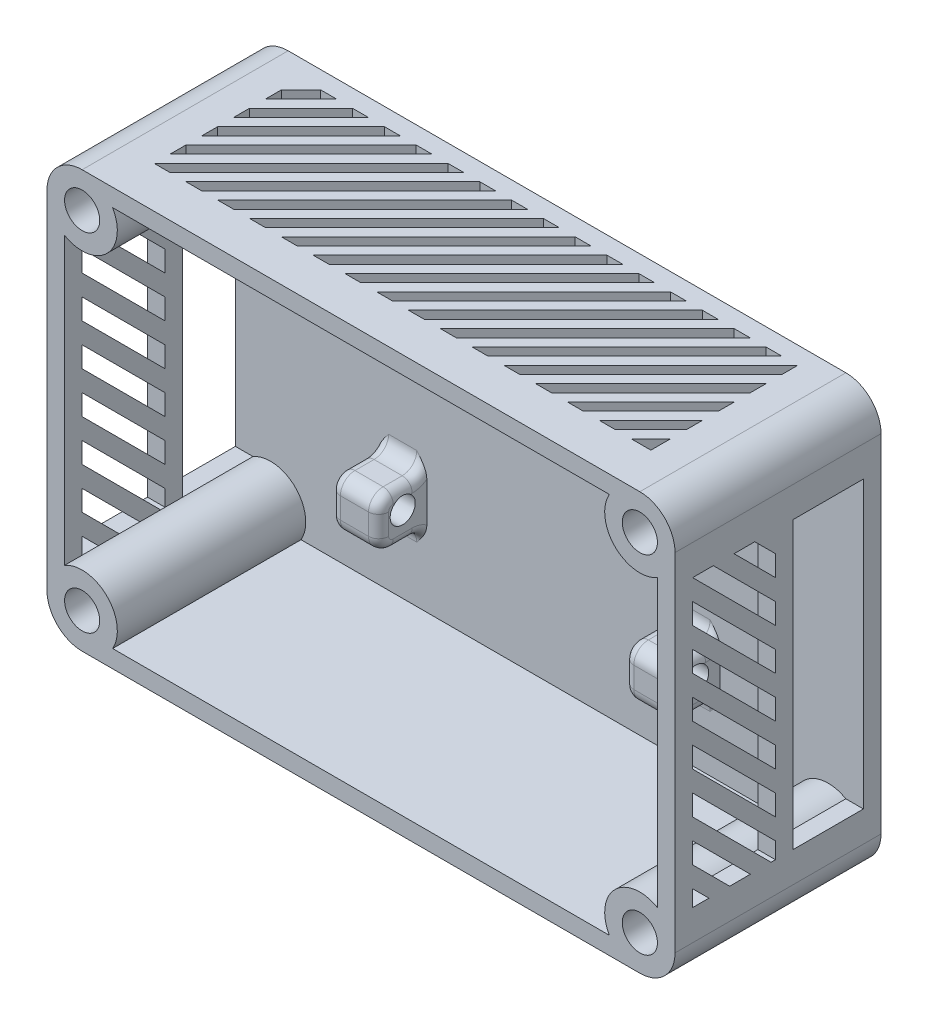
SolidWorks part; units mm, degrees
note: The reader was unsure of these and kept them because the rebuilt part matched: shared geometry of "Esquisse1<4>", "Esquisse1<5>".
ref_plane "Plan de face" through (0, 0, 0) normal (0, 0, 1) x (1, 0, 0)
ref_plane "Plan de dessus" through (0, 0, 0) normal (0, 1, 0) x (1, 0, 0)
ref_plane "Plan de droite" through (0, 0, 0) normal (1, 0, 0) x (0, 0, -1)
sketch "Esquisse1" plane through (0, 0, 0) normal (0, 0, 1) x (1, 0, 0)
  line L1 (-27.75, 17.25) -> (27.75, 17.25) construction
  line L2 (-27.75, 17.25) -> (-27.75, -17.25) construction
  line L3 (-27.75, -17.25) -> (27.75, -17.25) construction
  line L4 (27.75, 17.25) -> (27.75, -17.25) construction
  line L12 (-31.25, -20.75) -> (31.25, -20.75)
  line L13 (31.25, 20.75) -> (31.25, -20.75)
  line L14 (-31.25, 20.75) -> (31.25, 20.75)
  line L15 (-31.25, 20.75) -> (-31.25, -20.75)
  line L16 (-22.75, 12.25) -> (-22.75, -12.25)
  line L17 (-22.75, -12.25) -> (22.75, -12.25)
  line L18 (22.75, 12.25) -> (22.75, -12.25)
  line L19 (-22.75, 12.25) -> (22.75, 12.25)
  circle A0 centre (-27.75, 17.25) radius 1.75
  circle A1 centre (27.75, 17.25) radius 1.75
  circle A2 centre (27.75, -17.25) radius 1.75
  circle A3 centre (-27.75, -17.25) radius 1.75
  point P4 (-27.75, 0)
  point P6 (0, 17.25)
  dimension "D3" = 3.5
  dimension "D1" = 34.5
  dimension "D2" = 55.5
  dimension "D4" = 3.5
  dimension "D5" = 5
extrude "Boss.-Extru.1" add sketch "Esquisse1" along normal blind 17.5 contours A0 | L14 L15 L12 L13 A3 A2 A1 A0 | A3 | A2 | A1 | L19 L16 L17 L18
extrude "Boss.-Extru.2" add sketch "Esquisse1<4>" against normal blind 3 contours L19 L16 L17 L18 | L14 L15 L12 L13 A3 A2 A1 A0 L16 L19 L18 L17
sketch "Esquisse1<4>" plane through (0, 0, 0) normal (0, 0, 1) x (1, 0, 0) same geometry as "Esquisse1"
extrude "Enlèv. mat.-Extru.1" cut sketch "Esquisse1<5>" against normal up to next (3 mm away) and the other way up to next (17.5 mm away) contours A3 | A0 | A1 | A2
sketch "Esquisse1<5>" plane through (0, 0, 0) normal (0, 0, 1) x (1, 0, 0) same geometry as "Esquisse1"
shell "Coque1" thickness 1.75
fillet "Congé1" radius 3.5 4 edges at (-31.25, -20.75, 7.25) (-31.25, 20.75, 7.25) (31.25, -20.75, 7.25) (31.25, 20.75, 7.25)
sketch "Esquisse2" plane through (0, 0, -1.25) normal (0, 0, 1) x (1, 0, 0)
  line L1 (-17, -7) -> (-12.2, -7)
  line L2 (-17, -7) -> (-17, -12)
  line L3 (-17, -12) -> (-12.2, -12)
  line L4 (-12.2, -7) -> (-12.2, -12)
  line L5 (-17, 12) -> (-12.2, 12)
  line L6 (-17, 12) -> (-17, 7)
  line L7 (-17, 7) -> (-12.2, 7)
  line L8 (-12.2, 12) -> (-12.2, 7)
  line L9 (12.2, 12) -> (17, 12)
  line L10 (12.2, 12) -> (12.2, 7)
  line L11 (12.2, 7) -> (17, 7)
  line L12 (17, 12) -> (17, 7)
  line L13 (12.2, -12) -> (17, -12)
  line L14 (12.2, -12) -> (12.2, -7)
  line L15 (12.2, -7) -> (17, -7)
  line L16 (17, -12) -> (17, -7)
  line L17 (-12.2, 12) -> (12.2, 12) construction
  line L18 (-12.2, 12) -> (-12.2, -12) construction
  line L19 (-12.2, -12) -> (12.2, -12) construction
  line L20 (12.2, 12) -> (12.2, -12) construction
  point P16 (0, 12)
  point P18 (-12.2, 0)
  dimension "D1" = 24.4
  dimension "D2" = 14
  dimension "D3" = 24
  dimension "D4" = 4.8
extrude "Boss.-Extru.3" add sketch "Esquisse2" along normal blind 4.8
sketch "Esquisse3" plane through (12.2, 0, 0) normal (-1, 0, 0) x (0, 0, 1)
  line L0 (1.15, -9) -> (1.15, 9) construction
  line L1 (-3, 17.25) -> (-3, -17.25) construction
  circle A0 centre (1.15, -9) radius 1.25
  circle A1 centre (1.15, 9) radius 1.25
  point P2 (1.15, 0)
  dimension "D1" = 2.5
  dimension "D2" = 18
  dimension "D3" = 4.15
extrude "Enlèv. mat.-Extru.2" cut sketch "Esquisse3" against normal up to next and the other way up to next
sketch "Esquisse4" plane through (-31.25, 0, 0) normal (-1, 0, 0) x (0, 0, 1)
  line L0 (7.5, 14.2189) -> (8.5313, 13.1877) construction
  line L1 (-1.25, -14.2189) -> (5.75, -14.2189)
  line L2 (-1.25, -14.2189) -> (-1.25, 14.2189)
  line L3 (-1.25, 14.2189) -> (5.75, 14.2189)
  line L4 (5.75, -14.2189) -> (5.75, 14.2189)
  line L5 (-1.25, 14.2189) -> (-1.25, -14.2189) construction
  line L6 (-1.25, 0) -> (-3, 0) construction
  line L7 (7.5, 14.2189) -> (15.75, 14.2189)
  line L8 (7.5, 14.2189) -> (7.5, -14.2189)
  line L9 (7.5, -14.2189) -> (15.75, -14.2189)
  line L10 (15.75, 14.2189) -> (15.75, -14.2189)
  line L11 (-3, 17.25) -> (-3, -17.25) construction
  line L12 (5.75, 0) -> (7.5, 0) construction
  line L13 (15.75, 0) -> (17.5, 0) construction
  line L14 (17.5, 17.25) -> (17.5, -17.25) construction
  line L15 (9.5625, 14.2189) -> (7.5, 12.1564)
  line L16 (11.625, 14.2189) -> (7.5, 10.0939)
  line L17 (8.5313, 13.1877) -> (9.5625, 12.1564) construction
  line L18 (13.6875, 14.2189) -> (7.5, 8.0314)
  line L19 (9.5625, 12.1564) -> (10.5938, 11.1252) construction
  line L20 (15.75, 14.2189) -> (7.5, 5.9689)
  line L21 (10.5938, 11.1252) -> (11.625, 10.0939) construction
  line L22 (15.75, 12.1564) -> (7.5, 3.9064)
  line L23 (15.75, 10.0939) -> (7.5, 1.8439)
  line L24 (15.75, 8.0314) -> (7.5, -0.2186)
  line L25 (15.75, 5.9689) -> (7.5, -2.2811)
  line L26 (15.75, 3.9064) -> (7.5, -4.3436)
  line L27 (15.75, 1.8439) -> (7.5, -6.4061)
  line L28 (7.5, -8.4686) -> (15.75, -0.2186)
  line L29 (7.5, -10.5311) -> (15.75, -2.2811)
  line L30 (7.5, -12.5936) -> (15.75, -4.3436)
  line L31 (11.625, 10.0939) -> (12.6562, 9.0627) construction
  line L32 (12.6562, 9.0627) -> (13.6875, 8.0314) construction
  line L33 (13.6875, 8.0314) -> (14.7187, 7.0002) construction
  line L34 (8.5313, 2.8752) -> (9.5625, 1.8439) construction
  line L35 (9.5625, 1.8439) -> (10.5938, 0.8127) construction
  line L36 (10.5938, 0.8127) -> (11.625, -0.2186) construction
  line L37 (11.625, -0.2186) -> (12.6562, -1.2498) construction
  line L38 (12.6562, -1.2498) -> (13.6875, -2.2811) construction
  line L39 (7.9372, -14.2189) -> (15.75, -6.4061)
  line L40 (13.6875, -2.2811) -> (14.7187, -3.3123) construction
  line L41 (9.9997, -14.2189) -> (15.75, -8.4686)
  line L42 (12.0622, -14.2189) -> (15.75, -10.5311)
  line L43 (14.1247, -14.2189) -> (15.75, -12.5936)
  line L44 (14.9373, -13.4062) -> (13.9061, -12.375) construction
  line L48 (7.5, -8.4686) -> (8.5312, -9.4998) construction
  line L49 (8.5312, -9.4998) -> (9.5625, -10.5311) construction
  line L50 (9.5625, -10.5311) -> (10.5937, -11.5623) construction
  line L51 (10.5937, -11.5623) -> (11.625, -12.5936) construction
  line L52 (11.625, -12.5936) -> (12.6562, -13.6248) construction
  line L53 (12.6562, -13.6248) -> (13.2503, -14.2189) construction
  line L54 (14.9373, -13.4062) -> (15.75, -14.2189) construction
  point P4 (2.25, 14.2189)
  point P6 (-1.25, 0)
  dimension "D1" = 45
  dimension "D2" = 7
extrude "Enlèv. mat.-Extru.3" cut sketch "Esquisse4" against normal up to next contours L1 L4 L3 L2 | L16 L7 L15 L8 | L20 L7 L18 L8 | L23 L10 L22 L8 | L25 L10 L24 L8 | L27 L10 L26 L8 | L8 L29 L10 L28 | L9 L39 L10 L30 L8 | L9 L42 L10 L41 | L43 L9 L10
mirror "Symétrie1" about plane through (0, 0, 0) normal (1, 0, 0) of "Enlèv. mat.-Extru.3"
sketch "Esquisse5" plane through (0, 20.75, 0) normal (0, 1, 0) x (1, 0, 0)
  line L0 (-24.7189, 1.25) -> (24.7189, 1.25) construction
  line L1 (-24.7189, 1.25) -> (24.7189, 1.25)
  line L2 (-24.7189, 1.25) -> (-24.7189, -13.3718)
  line L3 (-24.7189, -13.3718) -> (24.7189, -13.3718)
  line L4 (24.7189, 1.25) -> (24.7189, -13.3718)
  line L6 (0, 1.25) -> (0, 3) construction
  line L8 (23.7382, -12.3911) -> (22.9469, -11.5998) construction
  line L10 (-24.7189, -3.8765) -> (-19.5924, 1.25)
  line L11 (-23.1364, -3.8765) -> (-18.0098, 1.25)
  line L12 (-21.5538, -3.8765) -> (-16.4273, 1.25)
  line L13 (-19.9713, -3.8765) -> (-14.8447, 1.25)
  line L14 (-18.3887, -3.8765) -> (-13.2622, 1.25)
  line L15 (-16.8062, -3.8765) -> (-11.6797, 1.25)
  line L16 (-15.2236, -3.8765) -> (-10.0971, 1.25)
  line L17 (-13.6411, -3.8765) -> (-8.5146, 1.25)
  line L18 (-12.0585, -3.8765) -> (-6.932, 1.25)
  line L19 (-10.476, -3.8765) -> (-5.3495, 1.25)
  line L20 (-8.8934, -3.8765) -> (-3.7669, 1.25)
  line L21 (-7.3109, -3.8765) -> (-2.1844, 1.25)
  line L22 (-5.7284, -3.8765) -> (-0.6018, 1.25)
  line L23 (-4.1458, -3.8765) -> (0.9807, 1.25)
  line L24 (-2.5633, -3.8765) -> (2.5633, 1.25)
  line L25 (-0.9807, -3.8765) -> (4.1458, 1.25)
  line L26 (0.6018, -3.8765) -> (5.7284, 1.25)
  line L27 (2.1844, -3.8765) -> (7.3109, 1.25)
  line L28 (3.7669, -3.8765) -> (8.8934, 1.25)
  line L29 (5.3495, -3.8765) -> (10.476, 1.25)
  line L30 (6.932, -3.8765) -> (12.0585, 1.25)
  line L31 (8.5146, -3.8765) -> (13.6411, 1.25)
  line L32 (10.0971, -3.8765) -> (15.2236, 1.25)
  line L33 (11.6797, -3.8765) -> (16.8062, 1.25)
  line L34 (13.2622, -3.8765) -> (18.3887, 1.25)
  line L35 (14.8447, -3.8765) -> (19.9713, 1.25)
  line L36 (16.4273, -3.8765) -> (21.5538, 1.25)
  line L37 (18.0098, -3.8765) -> (23.1364, 1.25)
  line L38 (19.5924, -3.8765) -> (24.7189, 1.25)
  line L39 (-24.7189, -8.6242) -> (-19.5924, -3.4976)
  line L40 (-23.1364, -8.6242) -> (-18.0098, -3.4976)
  line L41 (-21.5538, -8.6242) -> (-16.4273, -3.4976)
  line L42 (-19.9713, -8.6242) -> (-14.8447, -3.4976)
  line L43 (-18.3887, -8.6242) -> (-13.2622, -3.4976)
  line L44 (-16.8062, -8.6242) -> (-11.6797, -3.4976)
  line L45 (-15.2236, -8.6242) -> (-10.0971, -3.4976)
  line L46 (-13.6411, -8.6242) -> (-8.5146, -3.4976)
  line L47 (-12.0585, -8.6242) -> (-6.932, -3.4976)
  line L48 (-10.476, -8.6242) -> (-5.3495, -3.4976)
  line L49 (-8.8934, -8.6242) -> (-3.7669, -3.4976)
  line L50 (-7.3109, -8.6242) -> (-2.1844, -3.4976)
  line L51 (-5.7284, -8.6242) -> (-0.6018, -3.4976)
  line L52 (-4.1458, -8.6242) -> (0.9807, -3.4976)
  line L53 (-2.5633, -8.6242) -> (2.5633, -3.4976)
  line L54 (-0.9807, -8.6242) -> (4.1458, -3.4976)
  line L55 (0.6018, -8.6242) -> (5.7284, -3.4976)
  line L56 (2.1844, -8.6242) -> (7.3109, -3.4976)
  line L57 (3.7669, -8.6242) -> (8.8934, -3.4976)
  line L58 (5.3495, -8.6242) -> (10.476, -3.4976)
  line L59 (6.932, -8.6242) -> (12.0585, -3.4976)
  line L60 (8.5146, -8.6242) -> (13.6411, -3.4976)
  line L61 (10.0971, -8.6242) -> (15.2236, -3.4976)
  line L62 (11.6797, -8.6242) -> (16.8062, -3.4976)
  line L63 (13.2622, -8.6242) -> (18.3887, -3.4976)
  line L64 (14.8447, -8.6242) -> (19.9713, -3.4976)
  line L65 (16.4273, -8.6242) -> (21.5538, -3.4976)
  line L66 (18.0098, -8.6242) -> (23.1364, -3.4976)
  line L67 (19.5924, -8.6242) -> (24.7189, -3.4976)
  line L68 (-23.1364, -3.8765) -> (-24.7189, -5.4591)
  line L69 (-21.5538, -3.8765) -> (-24.7189, -7.0416)
  line L70 (-24.7189, -13.3718) -> (-19.5924, -8.2453)
  line L71 (-23.1364, -13.3718) -> (-18.0098, -8.2453)
  line L72 (-21.5538, -13.3718) -> (-16.4273, -8.2453)
  line L73 (-19.9713, -13.3718) -> (-14.8447, -8.2453)
  line L74 (-18.3887, -13.3718) -> (-13.2622, -8.2453)
  line L75 (-16.8062, -13.3718) -> (-11.6797, -8.2453)
  line L76 (-15.2236, -13.3718) -> (-10.0971, -8.2453)
  line L77 (-13.6411, -13.3718) -> (-8.5146, -8.2453)
  line L78 (-12.0585, -13.3718) -> (-6.932, -8.2453)
  line L79 (-10.476, -13.3718) -> (-5.3495, -8.2453)
  line L80 (-8.8934, -13.3718) -> (-3.7669, -8.2453)
  line L81 (-7.3109, -13.3718) -> (-2.1844, -8.2453)
  line L82 (-5.7284, -13.3718) -> (-0.6018, -8.2453)
  line L83 (-4.1458, -13.3718) -> (0.9807, -8.2453)
  line L84 (-2.5633, -13.3718) -> (2.5633, -8.2453)
  line L85 (-0.9807, -13.3718) -> (4.1458, -8.2453)
  line L86 (0.6018, -13.3718) -> (5.7284, -8.2453)
  line L87 (2.1844, -13.3718) -> (7.3109, -8.2453)
  line L88 (3.7669, -13.3718) -> (8.8934, -8.2453)
  line L89 (5.3495, -13.3718) -> (10.476, -8.2453)
  line L90 (6.932, -13.3718) -> (12.0585, -8.2453)
  line L91 (8.5146, -13.3718) -> (13.6411, -8.2453)
  line L92 (10.0971, -13.3718) -> (15.2236, -8.2453)
  line L93 (11.6797, -13.3718) -> (16.8062, -8.2453)
  line L94 (13.2622, -13.3718) -> (18.3887, -8.2453)
  line L95 (14.8447, -13.3718) -> (19.9713, -8.2453)
  line L96 (16.4273, -13.3718) -> (21.5538, -8.2453)
  line L97 (18.0098, -13.3718) -> (23.1364, -8.2453)
  line L98 (19.5924, -13.3718) -> (24.7189, -8.2453)
  line L99 (-23.1364, -8.6242) -> (-24.7189, -10.2067)
  line L100 (-21.5538, -8.6242) -> (-24.7189, -11.7893)
  line L101 (22.9469, -11.5998) -> (22.1556, -10.8085) construction
  line L102 (-27.75, 3) -> (27.75, 3) construction
  line L138 (21.1749, -13.3718) -> (24.7189, -9.8278)
  line L139 (22.7575, -13.3718) -> (24.7189, -11.4104)
  line L140 (21.5538, -8.2453) -> (24.7189, -5.0802)
  line L141 (23.1364, -8.2453) -> (24.7189, -6.6627)
  line L142 (21.5538, -3.4976) -> (24.7189, -0.3325)
  line L143 (23.1364, -3.4976) -> (24.7189, -1.9151)
  line L144 (-24.7189, -2.294) -> (-21.1749, 1.25)
  line L145 (-24.7189, -0.7114) -> (-22.7575, 1.25)
  line L148 (-24.7189, 1.25) -> (-23.7382, 0.2693) construction
  line L149 (-23.7382, 0.2693) -> (-22.9469, -0.522) construction
  line L150 (-22.9469, -0.522) -> (-22.1556, -1.3133) construction
  line L155 (-22.1556, -1.3133) -> (-21.3644, -2.1045) construction
  point P9 (24.7189, -6.0609)
  point P12 (0, 0)
  point P200 (0, 0)
  dimension "D2" = 45
  dimension "D3" = 7.25
  dimension "D1" = 29
  dimension "D4" = 2
  dimension "D5" = 2
extrude "Enlèv. mat.-Extru.5" cut sketch "Esquisse5" against normal up to next
fillet "Congé2" radius 1.45 16 edges at (14.6, 7, -1.25) (14.6, 7, 3.55) (14.6, 12, -1.25) (14.6, 12, 3.55) (14.6, -7, -1.25) (14.6, -7, 3.55) (14.6, -12, -1.25) (14.6, -12, 3.55) (-14.6, -12, -1.25) (-14.6, -12, 3.55) (-14.6, -7, 3.55) (-14.6, -7, -1.25) (-14.6, 12, -1.25) (-14.6, 12, 3.55) (-14.6, 7, -1.25) (-14.6, 7, 3.55)
fillet "Congé3" radius 1 56 edges at (-17, -6.5753, -0.8253) (-17, -7, 1.15) (-17, -7.4247, 3.1253) (-17, -12.4247, -0.8253) (-17, -12, 1.15) (-17, -11.5753, 3.1253) (-12.2, -12.4247, -0.8253) (-12.2, -12, 1.15) (-12.2, -11.5753, 3.1253) (-12.2, -6.5753, -0.8253) (-12.2, -7, 1.15) (-12.2, -7.4247, 3.1253) (12.2, 12.4247, -0.8253) (12.2, 12, 1.15) (12.2, 11.5753, 3.1253) (12.2, 6.5753, -0.8253) (12.2, 7, 1.15) (12.2, 7.4247, 3.1253) (17, 6.5753, -0.8253) (17, 7, 1.15) (17, 7.4247, 3.1253) (17, 12.4247, -0.8253) (17, 12, 1.15) (17, 11.5753, 3.1253) (-17, 12.4247, -0.8253) (-17, 12, 1.15) (-17, 11.5753, 3.1253) (-17, 6.5753, -0.8253) (-17, 7, 1.15) (-17, 7.4247, 3.1253) (-12.2, 6.5753, -0.8253) (-12.2, 7, 1.15) (-12.2, 7.4247, 3.1253) (-12.2, 12.4247, -0.8253) (-12.2, 12, 1.15) (-12.2, 11.5753, 3.1253) (12.2, -6.5753, -0.8253) (12.2, -7, 1.15) (12.2, -7.4247, 3.1253) (12.2, -12.4247, -0.8253) (12.2, -12, 1.15) (12.2, -11.5753, 3.1253) (17, -12.4247, -0.8253) (17, -12, 1.15) (17, -11.5753, 3.1253) (17, -6.5753, -0.8253) (17, -7, 1.15) (17, -7.4247, 3.1253) (-17, -9.5, 3.55) (-12.2, -9.5, 3.55) (12.2, 9.5, 3.55) (17, 9.5, 3.55) (-17, 9.5, 3.55) (-12.2, 9.5, 3.55) (12.2, -9.5, 3.55) (17, -9.5, 3.55)
